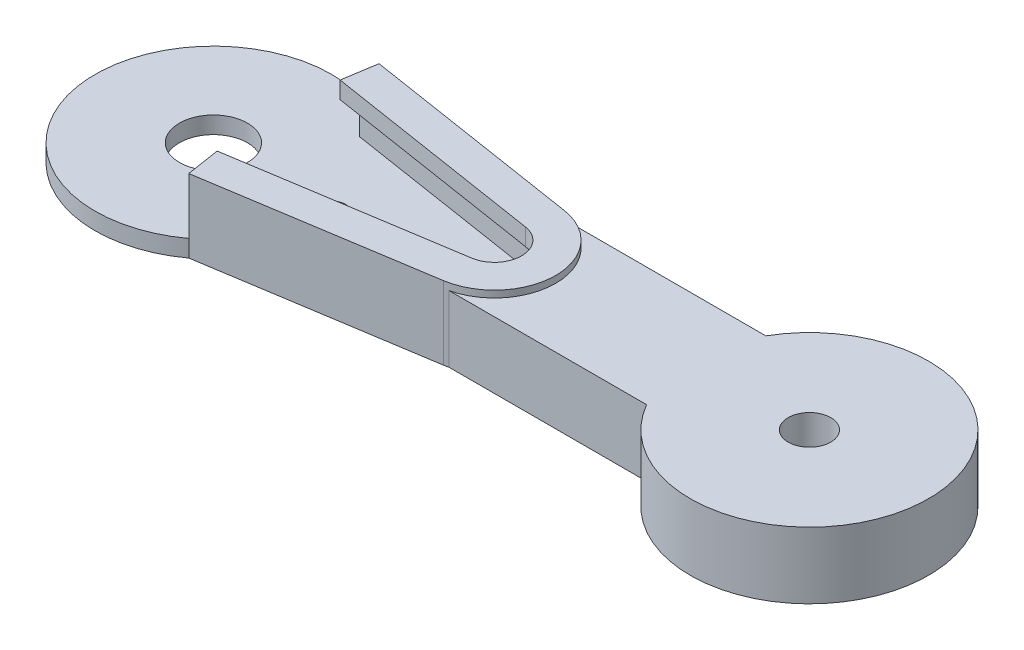
SolidWorks part; units mm, degrees
material "ABS"
ref_plane "Front Plane" through (0, 0, 0) normal (0, 0, 1) x (1, 0, 0)
ref_plane "Top Plane" through (0, 0, 0) normal (0, 1, 0) x (1, 0, 0)
ref_plane "Right Plane" through (0, 0, 0) normal (1, 0, 0) x (0, 0, -1)
sketch "Sketch2" plane through (0, 0, 0) normal (0, 1, 0) x (1, 0, 0)
  circle A0 centre (0, 0) radius 6
  circle A1 centre (0, 0) radius 1.5
  dimension "D1" = 12
  dimension "D2" = 3
extrude "Boss-Extrude1" add sketch "Sketch2" along normal mid plane 2.3
sketch "Sketch3" plane through (0, 1.15, 0) normal (0, 1, 0) x (1, 0, 0)
  line L0 (0, 0) -> (0, 2.9) construction
  line L3 (0, 0) -> (0.376, 2.9763) construction
  line L52 (0.1074, 2.898) -> (0.3384, 2.6787)
  line L53 (-0.1074, 2.898) -> (-0.3384, 2.6787)
  line L54 (0.8248, 2.7802) -> (0.9939, 2.5104)
  line L55 (0.6167, 2.8337) -> (0.3384, 2.6787)
  line L56 (1.4903, 2.4878) -> (1.587, 2.1843)
  line L57 (1.302, 2.5913) -> (0.9939, 2.5104)
  line L58 (2.0621, 2.039) -> (2.0804, 1.721)
  line L59 (1.9055, 2.1861) -> (1.587, 2.1843)
  line L60 (2.5044, 1.4621) -> (2.443, 1.1496)
  line L61 (2.3893, 1.6435) -> (2.0804, 1.721)
  line L62 (2.7894, 0.7934) -> (2.6522, 0.5059)
  line L63 (2.723, 0.9977) -> (2.443, 1.1496)
  line L64 (2.899, 0.0748) -> (2.6947, -0.1695)
  line L65 (2.8855, 0.2892) -> (2.6522, 0.5059)
  line L66 (2.8265, -0.6486) -> (2.5679, -0.8343)
  line L67 (2.8668, -0.4375) -> (2.6947, -0.1695)
  line L68 (2.5765, -1.3311) -> (2.2797, -1.4467)
  line L69 (2.6679, -1.1367) -> (2.5679, -0.8343)
  line L70 (2.1645, -1.93) -> (1.8483, -1.9682)
  line L71 (2.3014, -1.7645) -> (2.2797, -1.4467)
  line L72 (1.6165, -2.4077) -> (1.3007, -2.366)
  line L73 (1.7903, -2.2814) -> (1.8483, -1.9682)
  line L74 (0.967, -2.734) -> (0.6715, -2.6152)
  line L75 (1.1667, -2.655) -> (1.3007, -2.366)
  line L76 (0.2566, -2.8886) -> (0, -2.7)
  line L77 (0.4698, -2.8617) -> (0.6715, -2.6152)
  line L78 (-0.4698, -2.8617) -> (-0.6715, -2.6152)
  line L79 (-0.2566, -2.8886) -> (0, -2.7)
  line L80 (-1.1667, -2.655) -> (-1.3007, -2.366)
  line L81 (-0.967, -2.734) -> (-0.6715, -2.6152)
  line L82 (-1.7903, -2.2814) -> (-1.8483, -1.9682)
  line L83 (-1.6165, -2.4077) -> (-1.3007, -2.366)
  line L84 (-2.3014, -1.7645) -> (-2.2797, -1.4467)
  line L85 (-2.1645, -1.93) -> (-1.8483, -1.9682)
  line L86 (-2.6679, -1.1367) -> (-2.5679, -0.8343)
  line L87 (-2.5765, -1.3311) -> (-2.2797, -1.4467)
  line L88 (-2.8668, -0.4375) -> (-2.6947, -0.1695)
  line L89 (-2.8265, -0.6486) -> (-2.5679, -0.8343)
  line L90 (-2.8855, 0.2892) -> (-2.6522, 0.5059)
  line L91 (-2.899, 0.0748) -> (-2.6947, -0.1695)
  line L92 (-2.723, 0.9977) -> (-2.443, 1.1496)
  line L93 (-2.7894, 0.7934) -> (-2.6522, 0.5059)
  line L94 (-2.3893, 1.6435) -> (-2.0804, 1.721)
  line L95 (-2.5044, 1.4621) -> (-2.443, 1.1496)
  line L96 (-1.9055, 2.1861) -> (-1.587, 2.1843)
  line L97 (-2.0621, 2.039) -> (-2.0804, 1.721)
  line L98 (-1.302, 2.5913) -> (-0.9939, 2.5104)
  line L99 (-1.4903, 2.4878) -> (-1.587, 2.1843)
  line L100 (-0.6167, 2.8337) -> (-0.3384, 2.6787)
  line L101 (-0.8248, 2.7802) -> (-0.9939, 2.5104)
  line L102 (-2.533, 1.6075) -> (-2.3893, 1.6435) construction
  line L103 (-2.533, 1.6075) -> (-2.5044, 1.4621) construction
  line L104 (-2.8532, 0.9271) -> (-2.723, 0.9977) construction
  line L105 (-2.8532, 0.9271) -> (-2.7894, 0.7934) construction
  line L106 (-2.9941, 0.1884) -> (-2.8855, 0.2892) construction
  line L107 (-2.9941, 0.1884) -> (-2.899, 0.0748) construction
  line L108 (-2.9469, -0.5621) -> (-2.8668, -0.4375) construction
  line L109 (-2.9469, -0.5621) -> (-2.8265, -0.6486) construction
  line L110 (0, 3) -> (0.1074, 2.898) construction
  line L111 (0, 2.9) -> (0, 3) construction
  line L112 (0, 3) -> (-0.1074, 2.898) construction
  line L113 (-0.7461, 2.9057) -> (-0.6167, 2.8337) construction
  line L114 (-0.7461, 2.9057) -> (-0.8248, 2.7802) construction
  line L115 (-1.4453, 2.6289) -> (-1.302, 2.5913) construction
  line L116 (-1.4453, 2.6289) -> (-1.4903, 2.4878) construction
  line L117 (-2.0536, 2.1869) -> (-1.9055, 2.1861) construction
  line L118 (-2.0536, 2.1869) -> (-2.0621, 2.039) construction
  line L119 (-2.7145, -1.2773) -> (-2.6679, -1.1367) construction
  line L120 (-2.7145, -1.2773) -> (-2.5765, -1.3311) construction
  line L121 (-2.3115, -1.9123) -> (-2.3014, -1.7645) construction
  line L122 (-2.3115, -1.9123) -> (-2.1645, -1.93) construction
  line L123 (-1.7634, -2.4271) -> (-1.7903, -2.2814) construction
  line L124 (-1.7634, -2.4271) -> (-1.6165, -2.4077) construction
  line L125 (-1.1044, -2.7893) -> (-1.1667, -2.655) construction
  line L126 (-1.1044, -2.7893) -> (-0.967, -2.734) construction
  line L127 (-0.376, -2.9763) -> (-0.4698, -2.8617) construction
  line L128 (-0.376, -2.9763) -> (-0.2566, -2.8886) construction
  line L129 (0.376, -2.9763) -> (0.2566, -2.8886) construction
  line L130 (0.376, -2.9763) -> (0.4698, -2.8617) construction
  line L131 (1.1044, -2.7893) -> (0.967, -2.734) construction
  line L132 (1.1044, -2.7893) -> (1.1667, -2.655) construction
  line L133 (1.7634, -2.4271) -> (1.6165, -2.4077) construction
  line L134 (1.7634, -2.4271) -> (1.7903, -2.2814) construction
  line L135 (2.3115, -1.9123) -> (2.3014, -1.7645) construction
  line L136 (2.3115, -1.9123) -> (2.1645, -1.93) construction
  line L137 (2.7145, -1.2773) -> (2.6679, -1.1367) construction
  line L138 (2.7145, -1.2773) -> (2.5765, -1.3311) construction
  line L139 (2.9469, -0.5621) -> (2.8668, -0.4375) construction
  line L140 (2.9469, -0.5621) -> (2.8265, -0.6486) construction
  line L141 (2.9941, 0.1884) -> (2.8855, 0.2892) construction
  line L142 (2.9941, 0.1884) -> (2.899, 0.0748) construction
  line L143 (2.8532, 0.9271) -> (2.723, 0.9977) construction
  line L144 (2.8532, 0.9271) -> (2.7894, 0.7934) construction
  line L145 (2.533, 1.6075) -> (2.3893, 1.6435) construction
  line L146 (2.533, 1.6075) -> (2.5044, 1.4621) construction
  line L147 (2.0536, 2.1869) -> (1.9055, 2.1861) construction
  line L148 (2.0536, 2.1869) -> (2.0621, 2.039) construction
  line L149 (1.4453, 2.6289) -> (1.302, 2.5913) construction
  line L150 (1.4453, 2.6289) -> (1.4903, 2.4878) construction
  line L151 (0.7461, 2.9057) -> (0.6167, 2.8337) construction
  line L152 (0.7461, 2.9057) -> (0.8248, 2.7802) construction
  circle A0 centre (0, 0) radius 4.4
  circle A1 centre (0, 0) radius 3 construction
  circle A2 centre (0, 0) radius 2.7 construction
  arc A3 (-0.6167, 2.8337) -> (-0.8248, 2.7802) centre (0, 0) ccw
  arc A4 (-0.1074, 2.898) -> (-0.6167, 2.8337) centre (0, 0) ccw construction
  arc A5 (-0.8248, 2.7802) -> (-1.302, 2.5913) centre (0, 0) ccw construction
  arc A6 (-1.302, 2.5913) -> (-1.4903, 2.4878) centre (0, 0) ccw
  arc A7 (-1.4903, 2.4878) -> (-1.9055, 2.1861) centre (0, 0) ccw construction
  arc A8 (-1.9055, 2.1861) -> (-2.0621, 2.039) centre (0, 0) ccw
  arc A9 (-2.0621, 2.039) -> (-2.3893, 1.6435) centre (0, 0) ccw construction
  arc A10 (-2.3893, 1.6435) -> (-2.5044, 1.4621) centre (0, 0) ccw
  arc A11 (-2.5044, 1.4621) -> (-2.723, 0.9977) centre (0, 0) ccw construction
  arc A12 (-2.723, 0.9977) -> (-2.7894, 0.7934) centre (0, 0) ccw
  arc A13 (-2.7894, 0.7934) -> (-2.8855, 0.2892) centre (0, 0) ccw construction
  arc A14 (-2.8855, 0.2892) -> (-2.899, 0.0748) centre (0, 0) ccw
  arc A15 (-2.899, 0.0748) -> (-2.8668, -0.4375) centre (0, 0) ccw construction
  arc A16 (-2.8668, -0.4375) -> (-2.8265, -0.6486) centre (0, 0) ccw
  arc A17 (-2.8265, -0.6486) -> (-2.6679, -1.1367) centre (0, 0) ccw construction
  arc A18 (-2.6679, -1.1367) -> (-2.5765, -1.3311) centre (0, 0) ccw
  arc A19 (-2.5765, -1.3311) -> (-2.3014, -1.7645) centre (0, 0) ccw construction
  arc A20 (-2.3014, -1.7645) -> (-2.1645, -1.93) centre (0, 0) ccw
  arc A21 (-2.1645, -1.93) -> (-1.7903, -2.2814) centre (0, 0) ccw construction
  arc A22 (-1.7903, -2.2814) -> (-1.6165, -2.4077) centre (0, 0) ccw
  arc A23 (-1.6165, -2.4077) -> (-1.1667, -2.655) centre (0, 0) ccw construction
  arc A24 (-1.1667, -2.655) -> (-0.967, -2.734) centre (0, 0) ccw
  arc A25 (-0.967, -2.734) -> (-0.4698, -2.8617) centre (0, 0) ccw construction
  arc A26 (-0.4698, -2.8617) -> (-0.2566, -2.8886) centre (0, 0) ccw
  arc A27 (-0.2566, -2.8886) -> (0.2566, -2.8886) centre (0, 0) ccw construction
  arc A28 (0.2566, -2.8886) -> (0.4698, -2.8617) centre (0, 0) ccw
  arc A29 (0.4698, -2.8617) -> (0.967, -2.734) centre (0, 0) ccw construction
  arc A30 (0.967, -2.734) -> (1.1667, -2.655) centre (0, 0) ccw
  arc A31 (1.1667, -2.655) -> (1.6165, -2.4077) centre (0, 0) ccw construction
  arc A32 (1.6165, -2.4077) -> (1.7903, -2.2814) centre (0, 0) ccw
  arc A33 (1.7903, -2.2814) -> (2.1645, -1.93) centre (0, 0) ccw construction
  arc A34 (2.1645, -1.93) -> (2.3014, -1.7645) centre (0, 0) ccw
  arc A35 (2.3014, -1.7645) -> (2.5765, -1.3311) centre (0, 0) ccw construction
  arc A36 (2.5765, -1.3311) -> (2.6679, -1.1367) centre (0, 0) ccw
  arc A37 (2.6679, -1.1367) -> (2.8265, -0.6486) centre (0, 0) ccw construction
  arc A38 (2.8265, -0.6486) -> (2.8668, -0.4375) centre (0, 0) ccw
  arc A39 (2.8668, -0.4375) -> (2.899, 0.0748) centre (0, 0) ccw construction
  arc A40 (2.899, 0.0748) -> (2.8855, 0.2892) centre (0, 0) ccw
  arc A41 (2.8855, 0.2892) -> (2.7894, 0.7934) centre (0, 0) ccw construction
  arc A42 (2.7894, 0.7934) -> (2.723, 0.9977) centre (0, 0) ccw
  arc A43 (2.723, 0.9977) -> (2.5044, 1.4621) centre (0, 0) ccw construction
  arc A44 (2.5044, 1.4621) -> (2.3893, 1.6435) centre (0, 0) ccw
  arc A45 (2.3893, 1.6435) -> (2.0621, 2.039) centre (0, 0) ccw construction
  arc A46 (2.0621, 2.039) -> (1.9055, 2.1861) centre (0, 0) ccw
  arc A47 (1.9055, 2.1861) -> (1.4903, 2.4878) centre (0, 0) ccw construction
  arc A48 (1.4903, 2.4878) -> (1.302, 2.5913) centre (0, 0) ccw
  arc A49 (1.302, 2.5913) -> (0.8248, 2.7802) centre (0, 0) ccw construction
  arc A50 (0.8248, 2.7802) -> (0.6167, 2.8337) centre (0, 0) ccw
  arc A51 (0.3635, 2.8771) -> (0.1074, 2.898) centre (0, 0) ccw construction
  arc A52 (0.1074, 2.898) -> (-0.1074, 2.898) centre (0, 0) ccw
  arc A53 (0.6167, 2.8337) -> (0.3635, 2.8771) centre (0, 0) ccw construction
  point P84 (0, 0)
  dimension "D1" = 8.8
  dimension "D2" = 5.4
  dimension "D3" = 6
  dimension "D6" = 5.8
  dimension "D4" = 7.2
  dimension "D5" = 25
extrude "Boss-Extrude2" add sketch "Sketch3" along normal blind 3.2
sketch "Sketch4" plane through (0, 0, 0) normal (0, 1, 0) x (1, 0, 0)
  line L0 (0, 0) -> (16, 0) construction
  line L1 (3.9686, 4.5) -> (16.8881, 2.4697)
  line L2 (3.9686, -4.5) -> (16.8881, -2.4697)
  line L3 (16, 0) -> (13, 0) construction
  circle A0 centre (0, 0) radius 6 construction
  arc A1 (3.9686, -4.5) -> (3.9686, 4.5) centre (0, 0) ccw
  arc A2 (16.8881, 2.4697) -> (16.8881, -2.4697) centre (16.5, 0) cw
  circle A3 centre (16, 0) radius 0.75
  circle A4 centre (13, 0) radius 0.75
  circle A5 centre (10, 0) radius 0.75
  circle A6 centre (7, 0) radius 0.75
  dimension "D3" = 2.5
  dimension "D5" = 1.5
  dimension "D2" = 9
  dimension "D7" = 3
  dimension "D4" = 0.5
  dimension "D1" = 16
  dimension "D6" = 4
extrude "Boss-Extrude3" add sketch "Sketch4" along normal mid plane 2.3
pattern_circular "CirPattern1" count 2 over 360 about axis through (0, 4.35, 0) along (0, 1, 0) of "Boss-Extrude3"
sketch "Sketch5" [suppressed] plane through (0, 0, 0) normal (0, 1, 0) x (1, 0, 0)
  line L0 (3, 7) -> (-3, 7) construction
  circle A0 centre (0, 0) radius 10
  circle A1 centre (0, 7) radius 0.75
  circle A2 centre (-3, 7) radius 0.75
  circle A3 centre (3, 7) radius 0.75
  circle A4 centre (7, 3) radius 0.75
  circle A5 centre (7, 0) radius 0.75
  circle A6 centre (7, -3) radius 0.75
  circle A7 centre (3, -7) radius 0.75
  circle A8 centre (0, -7) radius 0.75
  circle A9 centre (-3, -7) radius 0.75
  circle A10 centre (-7, -3) radius 0.75
  circle A11 centre (-7, 0) radius 0.75
  circle A12 centre (-7, 3) radius 0.75
  circle A13 centre (0, 0) radius 1.5 construction
  circle A14 centre (0, 0) radius 1.5
  point P8 (0, 7)
  point P31 (0, 0)
  dimension "D1" = 1.5
  dimension "D3" = 2.25
  dimension "D4" = 6
  dimension "D2" = 7
  dimension "D5" = 4
extrude "Boss-Extrude4" [suppressed] add sketch "Sketch5" along normal mid plane 2.3
sketch "Sketch6" plane through (0, -1.15, 0) normal (0, -1, 0) x (1, 0, 0)
  line L3 (16.9036, 2.5685) -> (3.9842, 4.5988)
  line L5 (16.9036, 2.5685) -> (3.9842, 4.5988)
  line L6 (17.0589, -3.5564) -> (4.1394, -5.5867)
  line L7 (16.9036, -2.5685) -> (3.9842, -4.5988)
  line L8 (16.9036, -2.5685) -> (3.9842, -4.5988)
  line L9 (17.0589, 3.5564) -> (4.1394, 5.5867)
  line L10 (4.1394, 5.5867) -> (3.9842, 4.5988)
  line L11 (3.9842, -4.5988) -> (4.1394, -5.5867)
  circle A3 centre (0, 0) radius 6.0846
  arc A4 (16.9036, -2.5685) -> (16.9036, 2.5685) centre (16.5, 0) ccw
  arc A5 (16.9036, -2.5685) -> (16.9036, 2.5685) centre (16.5, 0) ccw
  arc A6 (17.0589, -3.5564) -> (17.0589, 3.5564) centre (16.5, 0) ccw
  dimension "D1" = 0.1
  dimension "D2" = 0.1
  dimension "D3" = 1
extrude "Boss-Extrude5" add sketch "Sketch6" against normal blind 2.3 separate body contours L6 A6 L9 L10 L5 A5 L8 L11 region at (10.4743, -1.15, 3.7774)
sketch "Sketch7" plane through (0, -1.15, 0) normal (0, -1, 0) x (1, 0, 0)
  line L14 (4.1394, -5.5867) -> (17.0589, -3.5564)
  line L15 (17.0589, 3.5564) -> (4.1394, 5.5867)
  line L16 (4.1394, -5.5867) -> (17.0589, -3.5564)
  line L17 (17.0589, 3.5564) -> (4.1394, 5.5867)
  arc A2 (4.1394, 5.5867) -> (4.1394, -5.5867) centre (0, 0) ccw
  circle A5 centre (0, 0) radius 2
  arc A6 (17.0589, -3.5564) -> (17.0589, 3.5564) centre (16.5, 0) ccw
  arc A7 (17.0589, -3.5564) -> (17.0589, 3.5564) centre (16.5, 0) ccw
  dimension "D1" = 1
extrude "Boss-Extrude6" add sketch "Sketch7" along normal blind 1
sketch "Sketch10" plane through (0, -2.15, 0) normal (0, -1, 0) x (1, 0, 0)
  line L0 (0, 0) -> (20.1, 0) construction
  arc A0 (17.0589, -3.5564) -> (17.0589, 3.5564) centre (16.5, 0) ccw construction
  circle A3 centre (7, 0) radius 0.75
  circle A4 centre (10, 0) radius 0.75
  circle A5 centre (13, 0) radius 0.75
  circle A6 centre (16, 0) radius 0.75
  dimension "D1" = 1.5
  dimension "D2" = 7
  dimension "D3" = 4
extrude "Cut-Extrude2" cut sketch "Sketch10" against normal through all contours L0 A4 | L0 A5 | L0 A6 | A6 L0 | A5 L0 | A4 L0 | A3 L0 | L0 A3 region at (7, -2.15, 0.3183) region at (16, -2.15, 0.3183) region at (16, -2.15, -0.3183) region at (13, -2.15, 0.3183) region at (13, -2.15, -0.3183) region at (10, -2.15, 0.3183) region at (10, -2.15, -0.3183) region at (7, -2.15, -0.3183)
sketch "Sketch12" plane through (0, 1.15, 0) normal (0, 1, 0) x (1, 0, 0)
  line L8 (-3.9686, 4.5) -> (-16.8881, 2.4697)
  line L9 (-16.8881, -2.4697) -> (-3.9686, -4.5)
  line L10 (3.9686, -4.5) -> (16.8881, -2.4697)
  line L12 (-3.9686, 4.5) -> (-16.8881, 2.4697)
  line L13 (-16.8881, -2.4697) -> (-3.9686, -4.5)
  line L16 (3.9686, -4.5) -> (16.8881, -2.4697)
  line L17 (16.8881, 2.4697) -> (3.9686, 4.5)
  line L18 (16.8881, 2.4697) -> (3.9686, 4.5)
  arc A8 (3.9686, 4.5) -> (-3.9686, 4.5) centre (0, 0) ccw
  arc A9 (-16.8881, 2.4697) -> (-16.8881, -2.4697) centre (-16.5, 0) ccw
  arc A10 (-3.9686, -4.5) -> (3.9686, -4.5) centre (0, 0) ccw
  arc A11 (16.8881, -2.4697) -> (16.8881, 2.4697) centre (16.5, 0) ccw
  arc A12 (3.9686, 4.5) -> (-3.9686, 4.5) centre (0, 0) ccw
  arc A13 (-16.8881, 2.4697) -> (-16.8881, -2.4697) centre (-16.5, 0) ccw
  arc A14 (-3.9686, -4.5) -> (3.9686, -4.5) centre (0, 0) ccw
  arc A17 (16.8881, -2.4697) -> (16.8881, 2.4697) centre (16.5, 0) ccw
  dimension "D1" = 0
extrude "Cut-Extrude4" cut sketch "Sketch12" against normal blind 2.3
sketch "Sketch13" plane through (0, 4.35, 0) normal (0, 1, 0) x (1, 0, 0)
  circle A3 centre (0, 0) radius 4.4
  circle A4 centre (0, 0) radius 4.4
  dimension "D1" = 0
extrude "Cut-Extrude5" cut sketch "Sketch13" against normal blind 3.3
sketch "Sketch9" plane through (0, 1.15, 0) normal (0, 1, 0) x (1, 0, 0)
  line L0 (3.8289, -3.6109) -> (16.7484, -1.5806)
  line L1 (16.7484, 1.5806) -> (3.8289, 3.6109)
  line L2 (3.8289, 3.6109) -> (3.9842, 4.5988)
  line L3 (3.8289, -3.6109) -> (3.9842, -4.5988)
  line L5 (4.1394, 5.5867) -> (3.9842, 4.5988)
  line L7 (4.1394, -5.5867) -> (17.0589, -3.5564)
  line L8 (17.0589, 3.5564) -> (4.1394, 5.5867)
  line L9 (4.1394, -5.5867) -> (17.0589, -3.5564)
  line L10 (17.0589, 3.5564) -> (4.1394, 5.5867)
  line L11 (3.9842, -4.5988) -> (4.1394, -5.5867)
  line L30 (3.9842, -4.5988) -> (16.9036, -2.5685)
  line L31 (16.9036, 2.5685) -> (3.9842, 4.5988)
  line L32 (3.9842, -4.5988) -> (16.9036, -2.5685)
  line L33 (16.9036, 2.5685) -> (3.9842, 4.5988)
  arc A0 (16.7484, -1.5806) -> (16.7484, 1.5806) centre (16.5, 0) ccw
  arc A2 (17.0589, -3.5564) -> (17.0589, 3.5564) centre (16.5, 0) ccw
  arc A3 (17.0589, -3.5564) -> (17.0589, 3.5564) centre (16.5, 0) ccw
  arc A9 (16.9036, -2.5685) -> (16.9036, 2.5685) centre (16.5, 0) ccw
  arc A10 (16.9036, -2.5685) -> (16.9036, 2.5685) centre (16.5, 0) ccw
  line M4 (17.0589, 3.5564) -> (4.1394, 5.5867)
  line M5 (4.1394, 5.5867) -> (3.9842, 4.5988)
  line M6 (3.9842, 4.5988) -> (16.9036, 2.5685)
  arc M7 (16.9036, 2.5685) -> (16.9036, -2.5685) centre (16.5, 0) cw
  line M8 (16.9036, -2.5685) -> (3.9842, -4.5988)
  line M9 (3.9842, -4.5988) -> (4.1394, -5.5867)
  line M10 (4.1394, -5.5867) -> (17.0589, -3.5564)
  arc M11 (17.0589, -3.5564) -> (17.0589, 3.5564) centre (16.5, 0) ccw
  dimension "D1" = 1
  dimension "D2" = 0
  dimension "D3" = 1
extrude "Boss-Extrude8" add sketch "Sketch9" along normal blind 1 contours M11 M4 M5 M6 M7 M8 M9 M10 | A0 L0 L3 L2 L1 M8 M7 M6 region at (10.3163, 1.15, 2.7719) region at (10.4743, 1.15, 3.7774)
sketch "Sketch14" plane through (0, -2.15, 0) normal (0, -1, 0) x (1, 0, 0)
  line L0 (0, 0) -> (35, 0) construction
  line L1 (17.0589, 3.5564) -> (17.0589, -3.5564) construction
  line L3 (17.0589, 0) -> (30.837, 0)
  line L4 (17.0589, 0) -> (17.0589, 3.5)
  line L5 (17.0589, 3.5) -> (30.837, 3.5)
  line L6 (30.837, 0) -> (30.837, 3.5)
  line L7 (17.0589, 0) -> (30.837, 0)
  line L8 (17.0589, 0) -> (17.0589, -3.5)
  line L9 (17.0589, -3.5) -> (30.837, -3.5)
  line L10 (30.837, 0) -> (30.837, -3.5)
  circle A0 centre (35, 0) radius 7
  circle A1 centre (35, 0) radius 1.25
  arc M7 (17.0589, -3.5564) -> (17.0589, 3.5564) centre (16.5, 0) ccw
  dimension "D2" = 2.5
  dimension "D1" = 35
  dimension "D3" = 3.5
  dimension "D4" = 3.5
extrude "Boss-Extrude9" add sketch "Sketch14" against normal blind 3.9 contours A0 L3 L9 M7 | A0 L5 L3 M7 | L9 A0 L5 L6 L10 A1 | L7 A0 L9 L10 | L5 A0 L7 L6 region at (23.8235, -2.15, 1.856) region at (23.8235, -2.15, -1.856) region at (29.5552, -2.15, 1.6436) region at (29.5552, -2.15, -1.6436) region at (31.0284, -2.15, 1.75)
equation "\"N_hole\"= 4"
equation "\"N_horn\"= 2"
equation "\"D6@Sketch4\"=\"N_hole\""
equation "\"D1@CirPattern1\"=\"N_horn\""
equation "\"D1@Sketch4\"=(\"N_hole\" - 1) *3 +7"
